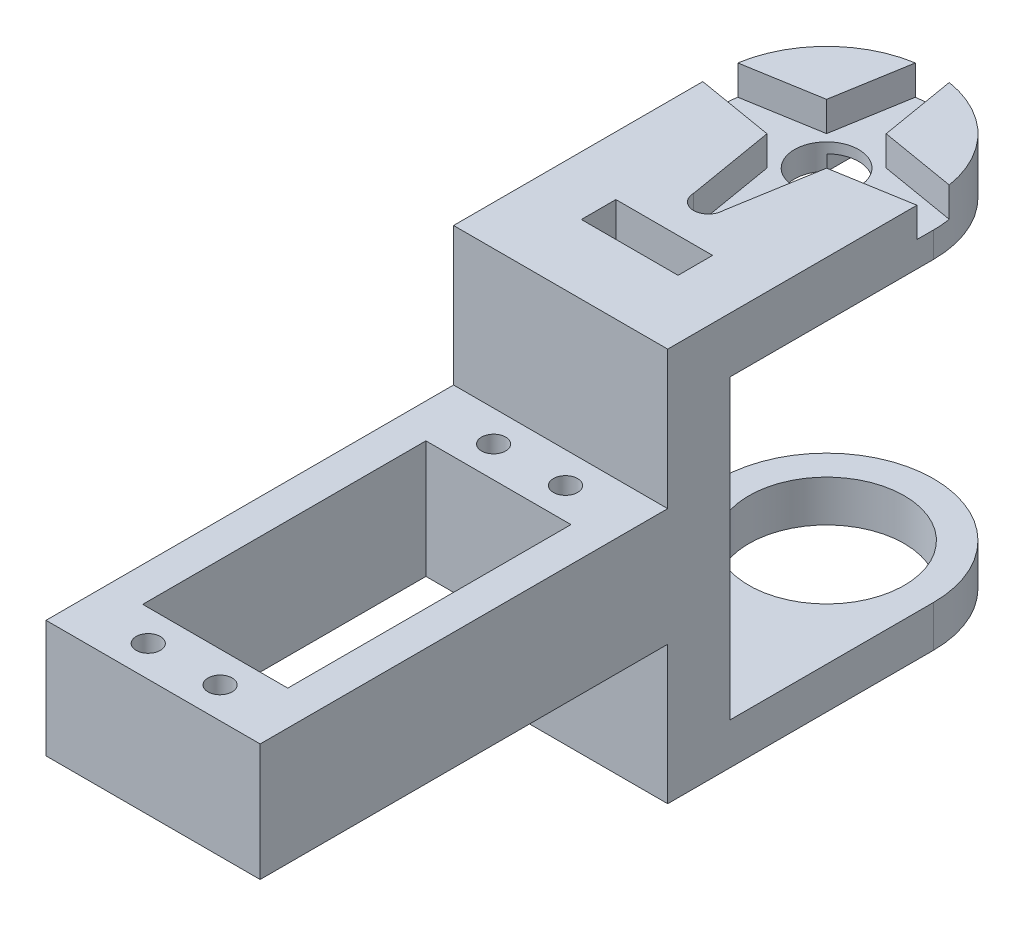
SolidWorks part; units mm, degrees
note: The reader was unsure of these and kept them because the rebuilt part matched: shared geometry of "Sketch6<3>", "Sketch9<3>".
ref_plane "Front Plane" through (0, 0, 0) normal (0, 0, 1) x (1, 0, 0)
ref_plane "Top Plane" through (0, 0, 0) normal (0, 1, 0) x (1, 0, 0)
ref_plane "Right Plane" through (0, 0, 0) normal (1, 0, 0) x (0, 0, -1)
sketch "Sketch1" plane through (0, 0, 0) normal (0, 0, 1) x (1, 0, 0)
  line L0 (-15.5, -28.5) -> (-8.5, -28.5) construction
  line L1 (15.5, -28.5) -> (-15.5, -28.5)
  line L2 (15.5, -28.5) -> (15.5, 28.5)
  line L3 (15.5, 28.5) -> (-15.5, 28.5)
  line L4 (-15.5, -28.5) -> (-15.5, -10.3)
  line L5 (15.5, -28.5) -> (-15.5, 28.5) construction
  line L6 (-15.5, 10.3) -> (-15.5, -10.3)
  line L8 (-15.5, -28.5) -> (-15.5, -10.3) construction
  line L13 (-15.5, 10.3) -> (-15.5, 28.5)
  point P0 (0, 0)
  dimension "D1" = 31
  dimension "D2" = 57
  dimension "D3" = 7
  dimension "D4" = 15.5
  dimension "D7" = 18.2
extrude "Boss-Extrude1" add sketch "Sketch1" along normal blind 9
sketch "Sketch4" plane through (0, 0, 0) normal (0, 0, -1) x (-1, 0, 0)
  line L0 (15.5, 28.5) -> (15.5, -28.5) construction
  line L1 (-15.5, 28.5) -> (15.5, 28.5)
  line L2 (-15.5, 28.5) -> (-15.5, 20.5)
  line L3 (-15.5, 20.5) -> (15.5, 20.5)
  line L4 (15.5, 28.5) -> (15.5, 20.5)
  line L5 (15.5, 28.5) -> (15.5, -28.5) construction
  line L6 (-15.5, -28.5) -> (15.5, -28.5)
  line L7 (-15.5, -28.5) -> (-15.5, -22.5)
  line L8 (-15.5, -22.5) -> (15.5, -22.5)
  line L9 (15.5, -28.5) -> (15.5, -22.5)
  dimension "D1" = 8
  dimension "D2" = 6
extrude "Boss-Extrude4" add sketch "Sketch4" along normal blind 45
sketch "Sketch6" plane through (0, -28.5, 0) normal (0, -1, 0) x (1, 0, 0)
  line L0 (0, 0) -> (0, -29.5) construction
  line L1 (15.5, 9) -> (15.5, -45) construction
  line L2 (-15.5, -29.5) -> (-15.5, -45)
  line L3 (-15.5, -45) -> (15.5, -45)
  line L4 (15.5, -45) -> (-15.5, -45) construction
  line L5 (15.5, -45) -> (15.5, -29.5)
  arc A0 (15.5, -29.5) -> (-15.5, -29.5) centre (0, -29.5) cw
  circle A1 centre (0, -29.5) radius 11.25
  line M2 (-15.5, 9) -> (-15.5, -45)
  line M3 (-15.5, -45) -> (15.5, -45)
  line M4 (15.5, -45) -> (15.5, 9)
  dimension "D2" = 15.5
  dimension "D3" = 22.5
  dimension "D1" = 29.5
extrude "Cut-Extrude1" cut sketch "Sketch6" against normal through all contours A0 L3 M4 | A0 M3 M2
extrude "Cut-Extrude2" cut sketch "Sketch6<3>" against normal blind 6
sketch "Sketch6<3>" plane through (0, -28.5, 0) normal (0, -1, 0) x (1, 0, 0) same geometry as "Sketch6"
sketch "Sketch7" plane through (0, 28.5, 0) normal (0, 1, 0) x (1, 0, 0)
  line L0 (0, 0) -> (0, 29.5) construction
  line L1 (0, 29.5) -> (0, 12.4) construction
  line L2 (0, 29.5) -> (17.1, 29.5) construction
  line L3 (0, 29.5) -> (0, 46.6) construction
  line L4 (0, 29.5) -> (-17.1, 29.5) construction
  line L5 (-17.1, 31.65) -> (-4.3134, 33.8134)
  line L6 (-4.3134, 33.8134) -> (-2.15, 46.6)
  line L7 (-4.3134, 25.1866) -> (-2.15, 12.4)
  line L8 (-17.1, 27.35) -> (-4.3134, 25.1866)
  line L9 (4.3134, 25.1866) -> (2.15, 12.4)
  line L10 (17.1, 27.35) -> (4.3134, 25.1866)
  line L11 (17.1, 31.65) -> (4.3134, 33.8134)
  line L12 (4.3134, 33.8134) -> (2.15, 46.6)
  arc A1 (-2.15, 12.4) -> (2.15, 12.4) centre (0, 12.4) ccw
  arc A2 (2.15, 46.6) -> (-2.15, 46.6) centre (0, 46.6) ccw
  arc A3 (17.1, 27.35) -> (17.1, 31.65) centre (17.1, 29.5) ccw
  arc A4 (-17.1, 31.65) -> (-17.1, 27.35) centre (-17.1, 29.5) ccw
  arc A5 (4.3134, 25.1866) -> (6.1, 29.5) centre (0, 29.5) ccw construction
  dimension "D4" = 4.3
  dimension "D8" = 4.3
  dimension "D9" = 4.3
  dimension "D10" = 4.3
  dimension "D11" = 12.2
  dimension "D1" = 29.5
  dimension "D3" = 17.1
  dimension "D5" = 17.1
  dimension "D6" = 17.1
  dimension "D7" = 17.1
  dimension "D12" = 24.1142
extrude "Cut-Extrude3" cut sketch "Sketch7" against normal blind 4.3
sketch "Sketch9" plane through (0, 20.5, 0) normal (0, -1, 0) x (1, 0, 0)
  line L0 (0, 0) -> (0, -29.5) construction
  line L1 (15.5, 0) -> (-15.5, 0) construction
  line L2 (3.25, -29.5) -> (-3.25, -29.5) construction
  line L3 (-3.25, -29.5) -> (-3.25, -32.8257) construction
  line L4 (3.25, -29.5) -> (3.25, -32.8257) construction
  line L5 (-3.25, -32.8257) -> (-3.25, -44.6554)
  line L6 (3.25, -32.8257) -> (3.25, -44.6554)
  circle A0 centre (0, -29.5) radius 4.65
  arc A1 (-15.5, -29.5) -> (15.5, -29.5) centre (0, -29.5) ccw construction
  dimension "D2" = 9.3
  dimension "D1" = 29.5
  dimension "D3" = 3.25
extrude "Cut-Extrude4" cut sketch "Sketch9" against normal blind 2.2 contours A0 L5 L4 L6
extrude "Cut-Extrude5" cut sketch "Sketch9<3>" against normal blind 8 contours A0
sketch "Sketch9<3>" plane through (0, 20.5, 0) normal (0, -1, 0) x (1, 0, 0) same geometry as "Sketch9"
sketch "Sketch10" plane through (0, 0, 9) normal (0, 0, 1) x (1, 0, 0)
  line L0 (-15.5, 28.5) -> (-15.5, -28.5) construction
  line L1 (15.5, -8.5) -> (-15.5, -8.5)
  line L2 (15.5, -8.5) -> (15.5, 8.5)
  line L3 (15.5, 8.5) -> (-15.5, 8.5)
  line L4 (-15.5, -8.5) -> (-15.5, 8.5)
  line L5 (15.5, -8.5) -> (-15.5, 8.5) construction
  line L6 (15.5, 8.5) -> (-15.5, -8.5) construction
  point P0 (0, 0)
  dimension "D1" = 17
extrude "Boss-Extrude5" add sketch "Sketch10" along normal blind 59
sketch "Sketch11" plane through (0, -8.5, 0) normal (0, -1, 0) x (1, 0, 0)
  line L0 (0, 0) -> (0, 9) construction
  line L1 (-15.5, 9) -> (15.5, 9) construction
  line L2 (0, 9) -> (0, 18) construction
  line L3 (-10.5, 18) -> (-10.5, 59)
  line L4 (-10.5, 18) -> (10.5, 18)
  line L5 (0, 13.5) -> (5.2, 13.5) construction
  line L6 (-10.5, 59) -> (10.5, 59)
  line L7 (10.5, 18) -> (10.5, 59)
  line L8 (-10.5, 38.5) -> (10.5, 38.5) construction
  circle A0 centre (5.2, 13.5) radius 1.75
  circle A1 centre (-5.2, 13.5) radius 1.75
  circle A2 centre (5.2, 63.5) radius 1.75
  circle A3 centre (-5.2, 63.5) radius 1.75
  dimension "D6" = 3.5
  dimension "D1" = 9
  dimension "D2" = 41
  dimension "D3" = 10.5
  dimension "D4" = 41
  dimension "D5" = 5.2
extrude "Cut-Extrude6" cut sketch "Sketch11" against normal through all
sketch "Sketch13" plane through (0, 28.5, 0) normal (0, 1, 0) x (1, 0, 0)
  line L0 (0, 0) -> (0, 3.5) construction
  line L2 (7, 1) -> (-7, 1)
  line L3 (7, 1) -> (7, 6)
  line L4 (7, 6) -> (-7, 6)
  line L5 (-7, 1) -> (-7, 6)
  line L6 (7, 1) -> (-7, 6) construction
  line L7 (7, 6) -> (-7, 1) construction
  dimension "D1" = 3.5
  dimension "D2" = 5
  dimension "D3" = 14
extrude "Cut-Extrude8" cut sketch "Sketch13" against normal blind 9
